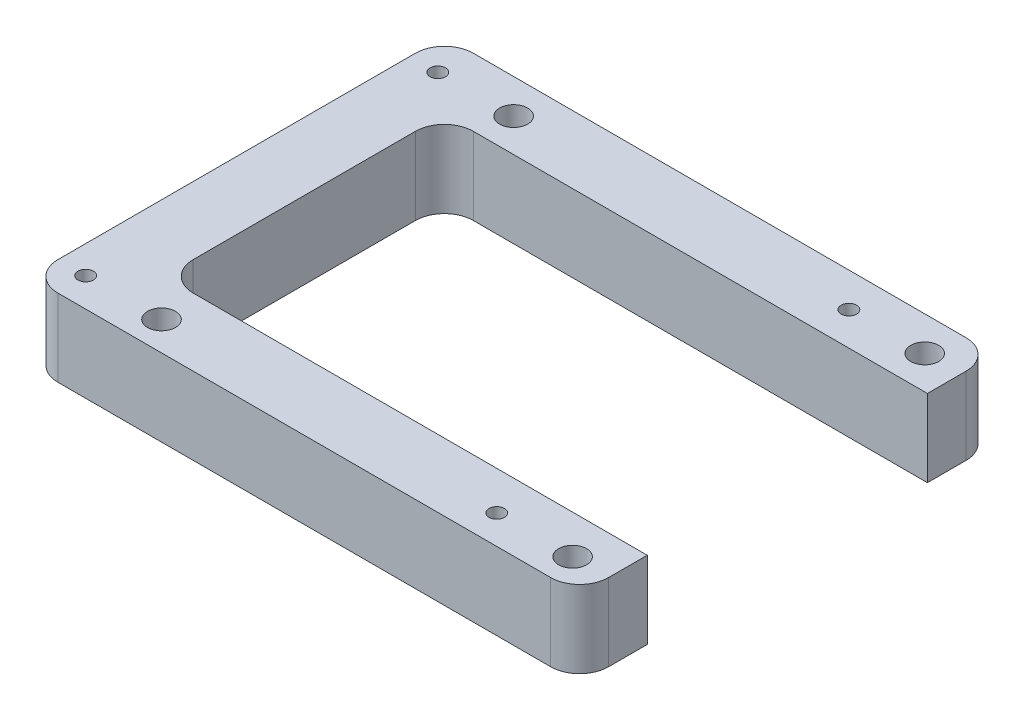
SolidWorks part; units mm, degrees
ref_plane "Front Plane" through (0, 0, 0) normal (0, 0, 1) x (1, 0, 0)
ref_plane "Top Plane" through (0, 0, 0) normal (0, 1, 0) x (1, 0, 0)
ref_plane "Right Plane" through (0, 0, 0) normal (1, 0, 0) x (0, 0, -1)
sketch "Sketch1" plane through (0, 0, 0) normal (0, 1, 0) x (1, 0, 0)
  line L0 (-28.5, -21.5) -> (28.5, 21.5) construction
  line L1 (-28.5, 21.5) -> (28.5, 21.5)
  line L2 (-28.5, 21.5) -> (-28.5, -21.5)
  line L3 (-28.5, -21.5) -> (28.5, -21.5)
  line L4 (28.5, 21.5) -> (28.5, -21.5)
  point P4 (0, 0)
  dimension "D1" = 43
  dimension "D2" = 57
extrude "Boss-Extrude1" add sketch "Sketch1" along normal blind 8 contours L2 L3 L4 L1
sketch "Sketch2" plane through (0, 0, 0) normal (0, 1, 0) x (1, 0, 0)
  line L0 (28.5, 21.5) -> (28.5, -21.5) construction
  line L1 (28.5, -14.5) -> (-21.5, -14.5)
  line L2 (28.5, -14.5) -> (28.5, 14.5)
  line L3 (28.5, 14.5) -> (-21.5, 14.5)
  line L4 (-21.5, -14.5) -> (-21.5, 14.5)
  line L5 (-28.5, 21.5) -> (-28.5, -21.5) construction
  line L6 (-28.5, 21.5) -> (28.5, 21.5) construction
  line L7 (-28.5, -21.5) -> (28.5, -21.5) construction
  dimension "D1" = 7
  dimension "D2" = 7
  dimension "D3" = 7
extrude "Cut-Extrude1" cut sketch "Sketch2" along normal blind 8
fillet "Fillet1" radius 3 6 edges at (-28.5, 4, -21.5) (-28.5, 4, 21.5) (28.5, 4, -21.5) (28.5, 4, 21.5) (-21.5, 4, 14.5) (-21.5, 4, -14.5)
sketch "Sketch3" plane through (0, 8, 0) normal (0, 1, 0) x (1, 0, 0)
  line L4 (-28.5, 18.5) -> (-28.5, -18.5) construction
  line L5 (-25.63, -18.5) -> (16.92, -18.5)
  line L6 (-25.63, -18.5) -> (-25.63, 17.95)
  line L7 (-25.63, 17.95) -> (16.92, 17.95)
  line L8 (16.92, -18.5) -> (16.92, 17.95)
  line L10 (-25.5, 21.5) -> (25.5, 21.5) construction
  line L11 (-17.78, -18.5) -> (24.77, -18.5)
  line L12 (-17.78, -18.5) -> (-17.78, 17.95)
  line L13 (-17.78, 17.95) -> (24.77, 17.95)
  line L14 (24.77, -18.5) -> (24.77, 17.95)
  point P1 (-25.63, -18.5)
  point P2 (-25.63, 17.95)
  point P3 (16.92, 17.95)
  point P4 (16.92, -18.5)
  point P8 (-17.78, -18.5)
  point P13 (-17.78, 17.95)
  point P14 (24.77, 17.95)
  point P15 (24.77, -18.5)
  dimension "D1" = 2.87
  dimension "D2" = 3.55
  dimension "D3" = 36.45
  dimension "D4" = 42.55
  dimension "D5" = 36.45
  dimension "D6" = 42.55
  dimension "D7" = 7.85
hole_wizard "M2x0.4 Tapped Hole1" positions "Sketch4" profile "Sketch6" tap size "M2x0.4" standard "ANSI Metric" end condition through all
sketch "Sketch4" plane through (0, 0, 0) normal (0, -1, 0) x (-1, 0, 0)
  line L0 (25.63, -18.5) -> (25.63, 17.95) construction
  point P0 (25.63, 17.95)
  point P3 (25.63, -18.5)
  point P7 (-16.92, -18.5)
  point P10 (-16.92, 17.95)
sketch "Sketch6" plane through (-25.63, 0, -17.95) normal (1, 0, 0) x (0, 0, -1)
  line L0 (0, 0) -> (0, 8)
  line L1 (0, 8) -> (0.8, 8)
  line L2 (0.8, 8) -> (0.8, 0)
  line L5 (0.8, 0) -> (0, 0)
  line L11 (0, -6.35) -> (0, 107.95) construction
  dimension "Thru Tap Drill Dia." = 1.6
  dimension "Thru Tap Drill Depth" = 8
cosmetic thread "Hole Thread1" parameters "D2"=2
cosmetic thread "Hole Thread2" parameters "D2"=2
cosmetic thread "Hole Thread3" parameters "D2"=2
cosmetic thread "Hole Thread4" parameters "D2"=2.4
hole_wizard "CBORE for M2 SHCS1" positions "Sketch7" profile "Sketch9" counterbore size "M2" standard "ANSI Metric" end condition through all
sketch "Sketch7" plane through (0, 0, 0) normal (0, -1, 0) x (-1, 0, 0)
  point P0 (-24.77, 17.95)
  point P3 (17.78, 17.95)
  point P6 (17.78, -18.5)
  point P9 (-24.77, -18.5)
sketch "Sketch9" plane through (24.77, 0, -17.95) normal (1, 0, 0) x (0, 0, -1)
  line L0 (0, 0) -> (0, 8)
  line L1 (0, 8) -> (1.45, 8)
  line L3 (1.45, 8) -> (1.45, 5.5)
  line L4 (1.45, 5.5) -> (2.45, 5.5)
  line L5 (2.45, 5.5) -> (2.45, 0)
  line L7 (2.45, 0) -> (0, 0)
  line L11 (0, -6.35) -> (0, 107.95) construction
  dimension "Thru Hole Dia." = 2.9
  dimension "Thru Hole Depth" = 8
  dimension "C'Bore Dia." = 4.9
  dimension "C'Bore Depth" = 5.5
